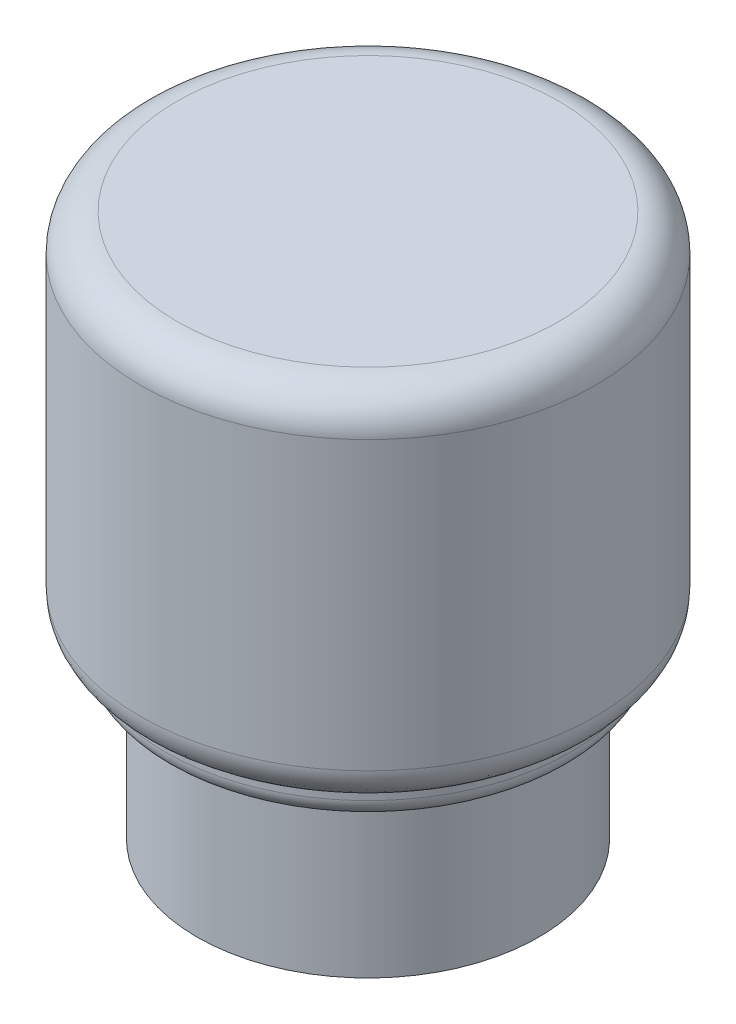
SolidWorks part; units mm, degrees
ref_plane "前视基准面" through (0, 0, 0) normal (0, 0, 1) x (1, 0, 0)
ref_plane "上视基准面" through (0, 0, 0) normal (0, 1, 0) x (1, 0, 0)
ref_plane "右视基准面" through (0, 0, 0) normal (1, 0, 0) x (0, 0, -1)
sketch "草图1" plane through (0, 0, 0) normal (0, 0, 1) x (1, 0, 0)
  line L0 (-1.1913, 14.4857) -> (5, 14.4857)
  line L1 (5, 14.4857) -> (5, 4.7366)
  line L2 (5, 4.7366) -> (4.3204, 4.7366)
  line L3 (-1.1913, 7.5941) -> (-1.1913, 14.4857)
  line L4 (4.3204, 4.7366) -> (4.3204, 4.0022)
  line L5 (4.3204, 4.0022) -> (3.4557, 4.0022)
  line L6 (-1.1913, 4.0022) -> (-1.1913, 7.5941)
  line L7 (3.4557, 4.0022) -> (3.4557, -0.2869)
  line L8 (3.4557, -0.2869) -> (-1.1913, -0.2869)
  line L9 (-1.1913, -0.2869) -> (-1.1913, 4.0022)
  point P9 (-1.1913, 14.4857)
revolve "旋转1" add sketch "草图1" angle 360 about L3
fillet "圆角2" radius 1 1 edges at (-1.1913, 14.4857, -6.1913)
fillet "圆角3" radius 1 1 edges at (-1.1913, 4.7366, -6.1913)
fillet "圆角4" radius 0.5 1 edges at (-1.1913, 4.0022, -5.5117)
